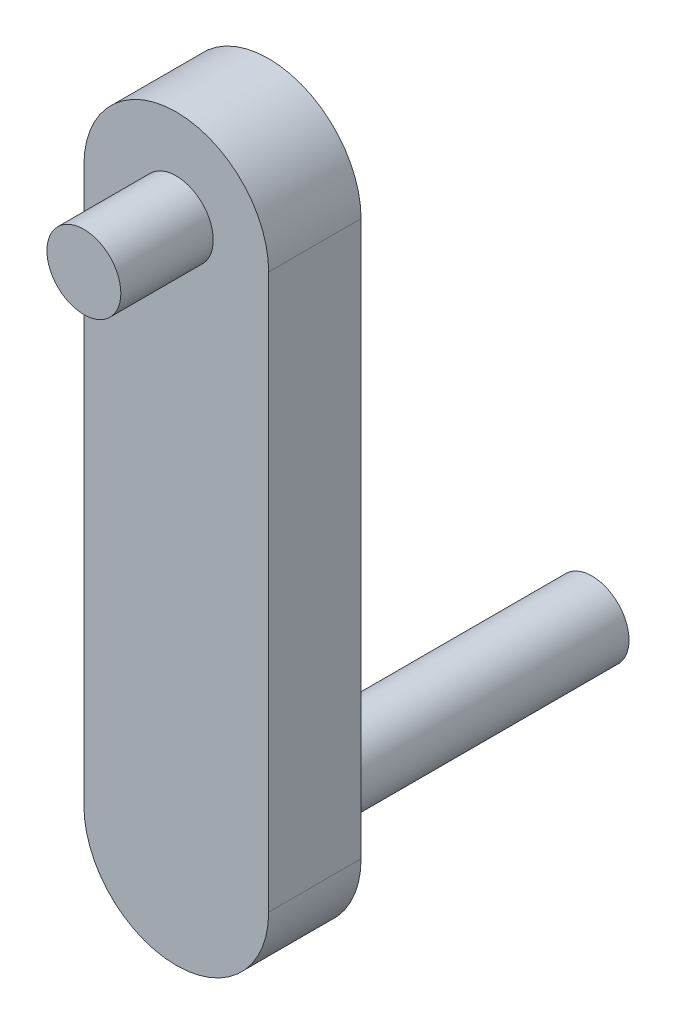
SolidWorks part; units mm, degrees
ref_plane "Front Plane" through (0, 0, 0) normal (0, 0, 1) x (1, 0, 0)
ref_plane "Top Plane" through (0, 0, 0) normal (0, 1, 0) x (1, 0, 0)
ref_plane "Right Plane" through (0, 0, 0) normal (1, 0, 0) x (0, 0, -1)
sketch "Sketch1" plane through (0, 0, 0) normal (0, 0, 1) x (1, 0, 0)
  line L2 (10, 30) -> (10, -30)
  line L4 (-10, 30) -> (-10, -30)
  line L5 (10, 30) -> (-10, -30) construction
  line L6 (10, -30) -> (-10, 30) construction
  arc A0 (-10, -30) -> (10, -30) centre (0, -30) ccw
  arc A1 (-10, 30) -> (10, 30) centre (0, 30) cw
  circle A2 centre (0, 30) radius 4
  circle A3 centre (0, -30) radius 4
  point P0 (0, 0)
  dimension "D3" = 8
  dimension "D4" = 8
  dimension "D5" = 10
  dimension "D1" = 20
  dimension "D2" = 60
extrude "Boss-Extrude1" add sketch "Sketch1" along normal blind 10
extrude "Boss-Extrude2" add sketch "Sketch1<2>" along normal blind 20 contours A2 region at (0, 30, 0)
sketch "Sketch1<2>" plane through (0, 0, 0) normal (0, 0, 1) x (1, 0, 0) same geometry as "Sketch1"
extrude "Boss-Extrude3" add sketch "Sketch1<3>" against normal blind 40 and the other way up to surface (10 mm away) from offset 5 contours A3 region at (0, -30, 0) other way up to face at (4, 30, 10)
sketch "Sketch1<3>" plane through (0, 0, 0) normal (0, 0, 1) x (1, 0, 0) same geometry as "Sketch1"
